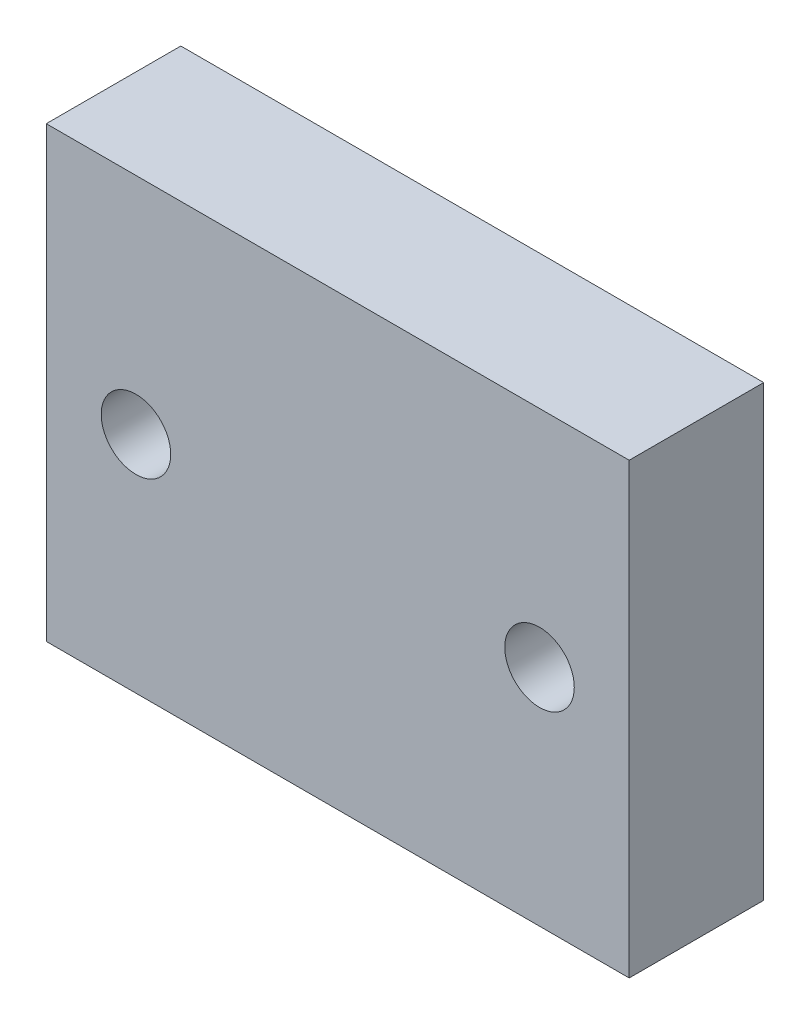
SolidWorks part; units mm, degrees
ref_plane "Front" through (0, 0, 0) normal (0, 0, 1) x (1, 0, 0)
ref_plane "Top" through (0, 0, 0) normal (0, 1, 0) x (1, 0, 0)
ref_plane "Right" through (0, 0, 0) normal (1, 0, 0) x (0, 0, -1)
sketch "Sketch1" plane through (0, 0, 0) normal (0, 0, 1) x (1, 0, 0)
  line L1 (13, -10) -> (-13, -10)
  line L2 (13, -10) -> (13, 10)
  line L3 (13, 10) -> (-13, 10)
  line L4 (-13, -10) -> (-13, 10)
  line L5 (13, -10) -> (-13, 10) construction
  line L6 (13, 10) -> (-13, -10) construction
  circle A2 centre (9, 0) radius 1.55
  circle A3 centre (-9, 0) radius 1.55
  point P0 (0, 0)
  point P10 (0, 0)
  dimension "D3" = 3.1
  dimension "D4" = 3.1
  dimension "D5" = 9
  dimension "D6" = 9
  dimension "D1" = 20
  dimension "D2" = 26
extrude "Boss-Extrude1" add sketch "Sketch1" along normal blind 6
sketch "Sketch4" plane through (0, 0, 0) normal (0, 0, -1) x (-1, 0, 0)
  line L1 (-5, 4) -> (5, 4)
  line L2 (-5, 4) -> (-5, 2)
  line L3 (-5, 2) -> (5, 2)
  line L4 (5, 4) -> (5, 2)
  line L5 (-5, 4) -> (5, 2) construction
  line L6 (-5, 2) -> (5, 4) construction
  line L8 (-13, 10) -> (13, 10) construction
  point P4 (0, 3)
  point P5 (4.9461, 3.2)
  point P6 (-5.2006, 3.2)
  point P7 (0, 0)
  dimension "D1" = 2
  dimension "D2" = 6
  dimension "D3" = 10
extrude "Cut-Extrude3" cut sketch "Sketch4" against normal blind 1
chamfer "Chamfer1" distance 1 angle 45 1 edges at (0, 4, 0)
